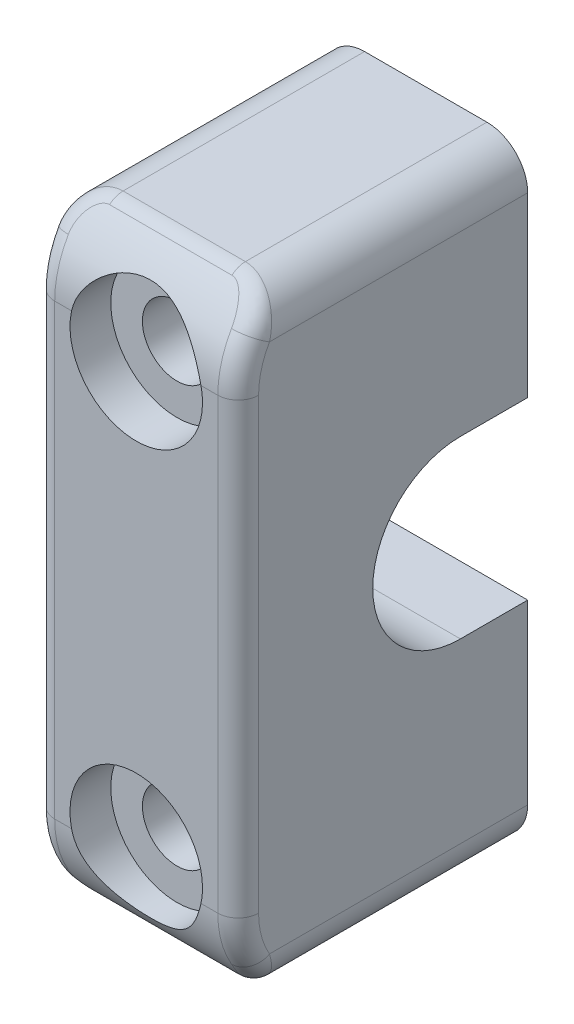
SolidWorks part; units mm, degrees
ref_plane "Front Plane" through (0, 0, 0) normal (0, 0, 1) x (1, 0, 0)
ref_plane "Top Plane" through (0, 0, 0) normal (0, 1, 0) x (1, 0, 0)
ref_plane "Right Plane" through (0, 0, 0) normal (1, 0, 0) x (0, 0, -1)
sketch "Sketch1" plane through (0, 0, 0) normal (1, 0, 0) x (0, 0, -1)
  line L1 (-6.1, -15) -> (6.1, -15)
  line L2 (-6.1, -15) -> (-6.1, 15)
  line L3 (-6.1, 15) -> (6.1, 15)
  line L4 (6.1, -15) -> (6.1, 15)
  line L5 (-6.1, -15) -> (6.1, 15) construction
  line L6 (-6.1, 15) -> (6.1, -15) construction
  point P0 (0, 0)
  dimension "D2" = 30
  dimension "D3" = 12.2
extrude "Boss-Extrude1" add sketch "Sketch1" along normal mid plane 10
sketch "Sketch5" plane through (5, 0, 0) normal (1, 0, 0) x (0, 0, -1)
  line L0 (25.0671, 0) -> (-25.0671, 0) construction
  line L1 (6.1, -15) -> (6.1, 15) construction
  circle A0 centre (2.8, 0) radius 4.3
  dimension "D1" = 8.6
  dimension "D2" = 3.3
extrude "Cut-Extrude2" cut sketch "Sketch5" against normal blind 7
sketch "Sketch3" plane through (0, 0, 6.1) normal (0, 0, 1) x (1, 0, 0)
  line L0 (0, -25.131) -> (0, 25.131) construction
  line L1 (25.0671, 0) -> (-25.0671, 0) construction
  circle A0 centre (0, 10.3) radius 1.7
  dimension "D1" = 3.4
  dimension "D2" = 10.3
extrude "Cut-Extrude1" cut sketch "Sketch3" against normal through all
mirror "Mirror1" about plane through (0, 0, 0) normal (0, 1, 0) of "Cut-Extrude1"
fillet "Fillet1" radius 2 4 edges at (-5, -15, 0) (5, -15, 0) (-5, 15, 0) (5, 15, 0)
fillet "Fillet2" radius 0.1 2 edges at (1.5, -2.7568, -6.1) (1.5, 2.7568, -6.1)
sketch "Sketch6" plane through (5, 0, 0) normal (1, 0, 0) x (0, 0, -1)
  line L0 (2.8, 0) -> (6.1, 0) construction
  line L1 (25.0671, 0) -> (-25.0671, 0) construction
  line L2 (2.8, 4.3) -> (6.1, 4.3)
  line L3 (2.8, -4.3) -> (6.1, -4.3)
  line L4 (6.1, 3.0199) -> (6.1, 13) construction
  arc A0 (2.8, 4.3) -> (2.8, -4.3) centre (2.8, 0) ccw
  arc A1 (6.1, -4.3) -> (6.1, 4.3) centre (6.1, 0) ccw
  arc A2 (5.9273, 2.9513) -> (5.9273, -2.9513) centre (2.8, 0) ccw construction
  point P5 (4.45, 0)
extrude "Cut-Extrude3" cut sketch "Sketch6" against normal up to surface (7 mm away) up to face at (-2, 0, -4.1685)
sketch "Sketch7" plane through (0, 0, 0) normal (1, 0, 0) x (0, 0, -1)
  line L0 (-8.1, 11) -> (-8.1, 0)
  line L1 (-6.1, 15) -> (-6.1, 0)
  line L2 (-6.1, 0) -> (-8.1, 0)
  line L3 (-6.1, 13) -> (-6.1, -13) construction
  line L4 (-6.1, 15) -> (6.1, 15) construction
  line L5 (25.0671, 0) -> (-25.0671, 0) construction
  arc A0 (-8.1, 11) -> (-6.1, 15) centre (-3.1, 11) cw
  dimension "D1" = 5
  dimension "D2" = 2
extrude "Boss-Extrude2" add sketch "Sketch7" along normal up to surface (5 mm away) and the other way up to surface (5 mm away) up to face at (5, 0, -1.6875) other way up to face at (-5, 0, 0)
sketch "Sketch8" plane through (0, 0, -6.1) normal (0, 0, -1) x (-1, 0, 0)
  line L0 (-3, 15) -> (-5, 15)
  line L1 (-5, 15) -> (-5, 13)
  line L2 (-5, 15) -> (-3, 15) construction
  line L3 (3, 15) -> (5, 15)
  line L4 (5, 15) -> (5, 13)
  line L5 (5, 13) -> (5, 15) construction
  line L6 (3, 15) -> (5, 15) construction
  circle A0 centre (0, 10.3) radius 1.7
  circle A1 centre (0, 10.3) radius 1.7 construction
  arc A2 (-5, 13) -> (-3, 15) centre (-3, 13) cw
  arc A4 (-3, 15) -> (-5, 13) centre (-3, 13) ccw construction
  arc A5 (-3, 15) -> (-5, 13) centre (-3, 13) ccw construction
  arc A6 (3, 15) -> (5, 13) centre (3, 13) cw
  arc A7 (5, 13) -> (3, 15) centre (3, 13) ccw construction
extrude "Cut-Extrude4" cut sketch "Sketch8" against normal through all
sketch "Sketch9" plane through (0, 0, 8.1) normal (0, 0, 1) x (1, 0, 0)
  circle A0 centre (0, 10.3) radius 3.25
  dimension "D1" = 6.5
extrude "Cut-Extrude5" cut sketch "Sketch9" against normal blind 2
mirror "Mirror6" about plane through (0, 0, 0) normal (0, 1, 0) of "Cut-Extrude5", "Cut-Extrude4", "Boss-Extrude2"
fillet "Fillet4" radius 1 12 edges at (0, -15, 6.1) (-4.5276, -14.2909, 6.8643) (-5, -12.0215, 7.9945) (-5, 0, 8.1) (-5, 12.0215, 7.9945) (-3.94, 14.7653, 6.3897) (4.5276, 14.2909, 6.8643) (5, 12.0215, 7.9945) (5, 0, 8.1) (5, -12.0215, 7.9945) (3.94, -14.7653, 6.3897)
equation "\"M3_d\"= 3.4"
equation "\"rod_d\"= 8.6"
equation "\"screws_t\"= 20.6"
equation "\"t\"= 3"
equation "\"D2@Sketch1\"=\"linear_bearing_l\""
equation "\"D3@Sketch1\"=\"rod_d\" + \"t\" - \"rod_t\" + 1.6"
equation "\"linear_bearing_l\"=30"
equation "\"cover_l\"= 10"
equation "\"D1@Boss-Extrude1\"=\"cover_l\""
equation "\"D1@Sketch3\"=\"M3_d\""
equation "\"D2@Sketch3\"=\"screws_t\" / 2"
equation "\"D1@Sketch5\"=\"rod_d\""
equation "\"D2@Sketch5\"=\"rod_d\" / 2 - \"rod_t\""
equation "\"rod_t\"= 1"
equation "\"D1@Cut-Extrude2\"=\"cover_l\" - \"t\""
